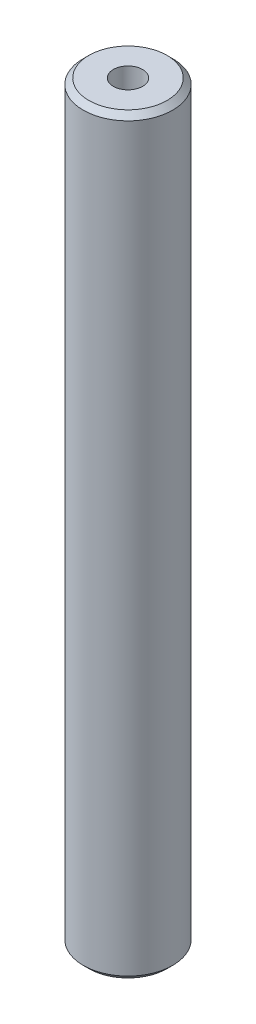
SolidWorks part; units mm, degrees
ref_plane "Front Plane" through (0, 0, 0) normal (0, 0, 1) x (1, 0, 0)
ref_plane "Top Plane" through (0, 0, 0) normal (0, 1, 0) x (1, 0, 0)
ref_plane "Right Plane" through (0, 0, 0) normal (1, 0, 0) x (0, 0, -1)
sketch "Sketch1" plane through (0, 0, 0) normal (0, 1, 0) x (1, 0, 0)
  circle A0 centre (0, 0) radius 22.5
  dimension "SHAFT_OD" = 45
extrude "Boss-Extrude1" add sketch "Sketch1" along normal blind 378.4219
sketch "Sketch2" plane through (0, 0, 0) normal (0, 1, 0) x (1, 0, 0)
  circle A0 centre (0, 0) radius 7.3748
  dimension "BORE_D" = 14.7496
extrude "Cut-Extrude1" cut sketch "Sketch2" along normal through all
chamfer "Chamfer1" distance 2.8221 angle 45 2 edges at (0, 378.4219, 22.5) (0, 0, 22.5)
